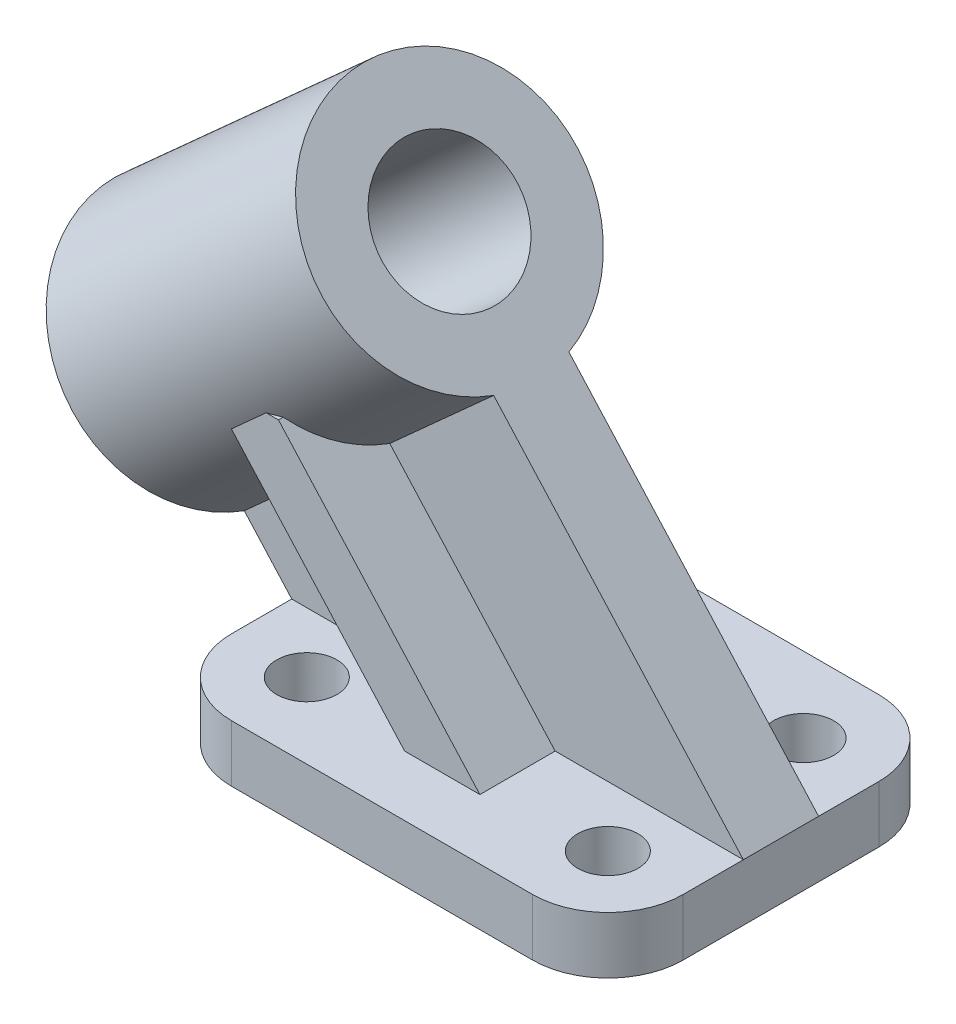
SolidWorks part; units mm, degrees
note: The reader was unsure of these and kept them because the rebuilt part matched: shared geometry of "Sketch7<4>".
material "ABS PC"
ref_plane "정면" through (0, 0, 0) normal (0, 0, 1) x (1, 0, 0)
ref_plane "윗면" through (0, 0, 0) normal (0, 1, 0) x (1, 0, 0)
ref_plane "우측면" through (0, 0, 0) normal (1, 0, 0) x (0, 0, -1)
sketch "Sketch1" plane through (0, 0, 0) normal (0, 1, 0) x (1, 0, 0)
  line L1 (0, 0) -> (60, 0)
  line L2 (0, 0) -> (0, 46)
  line L3 (0, 46) -> (60, 46)
  line L4 (60, 0) -> (60, 46)
  dimension "D1" = 60
  dimension "D2" = 46
extrude "Boss-Extrude1" add sketch "Sketch1" along normal blind 7.55
fillet "Fillet1" radius 10 4 edges at (0, 3.775, -46) (60, 3.775, -46) (0, 3.775, 0) (60, 3.775, 0)
sketch "Sketch2" plane through (0, 0, -46) normal (0, 0, -1) x (-1, 0, 0)
  line L0 (-60, 7.55) -> (-12.9681, 59.7842)
  line L1 (-50, 7.55) -> (-10, 7.55) construction
  dimension "D1" = 48
hole_wizard "Ø8.0 (8) Diameter Hole1" positions "3DSketch1" profile "Sketch3" hole size "Ø8.0" standard "Ansi Metric" end condition up to next
sketch3d "3DSketch1"
  line L0 (50, 7.55, -10) -> (50, 0, -10) construction
  line L1 (10, 7.55, -10) -> (10, 0, -10) construction
  line L2 (10, 7.55, -36) -> (10, 0, -36) construction
  line L3 (50, 7.55, -36) -> (50, 0, -36) construction
  point P0 (50, 7.55, -10)
  point P4 (10, 7.55, -10)
  point P8 (10, 7.55, -36)
  point P12 (50, 7.55, -36)
sketch "Sketch3" plane through (50, 7.55, -10) normal (1, 0, 0) x (0, 0, 1)
  line L0 (0, 0) -> (0, 7.55)
  line L1 (0, 7.55) -> (4, 7.55)
  line L2 (4, 7.55) -> (4, 0)
  line L5 (4, 0) -> (0, 0)
  line L11 (0, -6.35) -> (0, 107.95) construction
  dimension "관통 구멍 지름" = 8
  dimension "관통 구멍 깊이" = 7.55
sketch "Sketch4" plane through (0, 7.55, 0) normal (0, 1, 0) x (1, 0, 0)
  line L0 (60, 10) -> (60, 36) construction
  line L1 (60, 28) -> (0, 28)
  line L2 (60, 28) -> (60, 18)
  line L3 (60, 18) -> (0, 18)
  line L4 (0, 28) -> (0, 18)
  line L5 (0, 36) -> (0, 10) construction
  line L6 (30, 48.256) -> (30, -3.9223) construction
  point P8 (60, 23)
  dimension "D1" = 10
extrude "Boss-Extrude2" add sketch "Sketch4" along direction (-0.6691, 0.7431, 0) on the side of the normal blind 64
sketch "Sketch7" plane through (36.8902, 33.2161, 0) normal (0.7431, 0.6691, 0) x (0, 0, -1)
  line L2 (14.4449, 31.2836) -> (33.9903, 31.2836)
  line L3 (14.4449, 31.2836) -> (14.4449, 80.0372)
  line L4 (14.4449, 80.0372) -> (33.9903, 80.0372)
  line L5 (33.9903, 31.2836) -> (33.9903, 80.0372)
  circle A1 centre (23, 31.2836) radius 17
  line M3 (28, -34.5371) -> (28, 29.4629)
  line M4 (28, 29.4629) -> (18, 29.4629)
  line M5 (18, 29.4629) -> (18, -34.5371)
  dimension "D1" = 34
extrude "Cut-Extrude1" cut sketch "Sketch7" against normal blind 50
extrude "Boss-Extrude3" add sketch "Sketch7<4>" against normal up to vertex (44.5887 mm away) contours A1 L5 L2 M3 | L3 A1 L2 M5 | A1 M5 M3 M4
sketch "Sketch7<4>" plane through (36.8902, 33.2161, 0) normal (0.7431, 0.6691, 0) x (0, 0, -1) same geometry as "Sketch7"
sketch "Sketch11" plane through (0, 7.55, 0) normal (0, 1, 0) x (1, 0, 0)
  line L0 (60, 10) -> (60, 18) construction
  line L1 (26.8294, 28) -> (60, 28) construction
  line L2 (35, 28) -> (25, 28)
  line L3 (35, 28) -> (35, 38)
  line L4 (35, 38) -> (25, 38)
  line L5 (25, 28) -> (25, 38)
  line L6 (26.8294, 18) -> (60, 18) construction
  line L7 (35, 18) -> (25, 18)
  line L8 (35, 18) -> (35, 8)
  line L9 (35, 8) -> (25, 8)
  line L10 (25, 18) -> (25, 8)
  line L11 (60, 28) -> (60, 36) construction
  dimension "D1" = 10
  dimension "D2" = 10
  dimension "D3" = 10
  dimension "D4" = 10
  dimension "D5" = 25
  dimension "D6" = 25
extrude "Boss-Extrude4" add sketch "Sketch11" along direction (0.6691, -0.7431, 0) on the side of the normal blind 40
hole_wizard "Ø18.0 (18) Diameter Hole1" positions "3DSketch2" profile "Sketch10" hole size "Ø18.0" standard "Ansi Metric" end condition up to next
sketch3d "3DSketch2"
  line L0 (2.1507, 44.0328, -23) -> (15.9574, 56.4643, -23) construction
  point P0 (15.9574, 56.4643, -23)
sketch "Sketch10" plane through (15.9574, 56.4643, -23) normal (0, 0, 1) x (-0.6691, 0.7431, 0)
  line L0 (0, 0) -> (0, 44.5887)
  line L1 (0, 44.5887) -> (9, 44.5887)
  line L2 (9, 44.5887) -> (9, 0)
  line L5 (9, 0) -> (0, 0)
  line L11 (0, -6.35) -> (0, 107.95) construction
  dimension "관통 구멍 지름" = 18
  dimension "관통 구멍 깊이" = 44.5887
